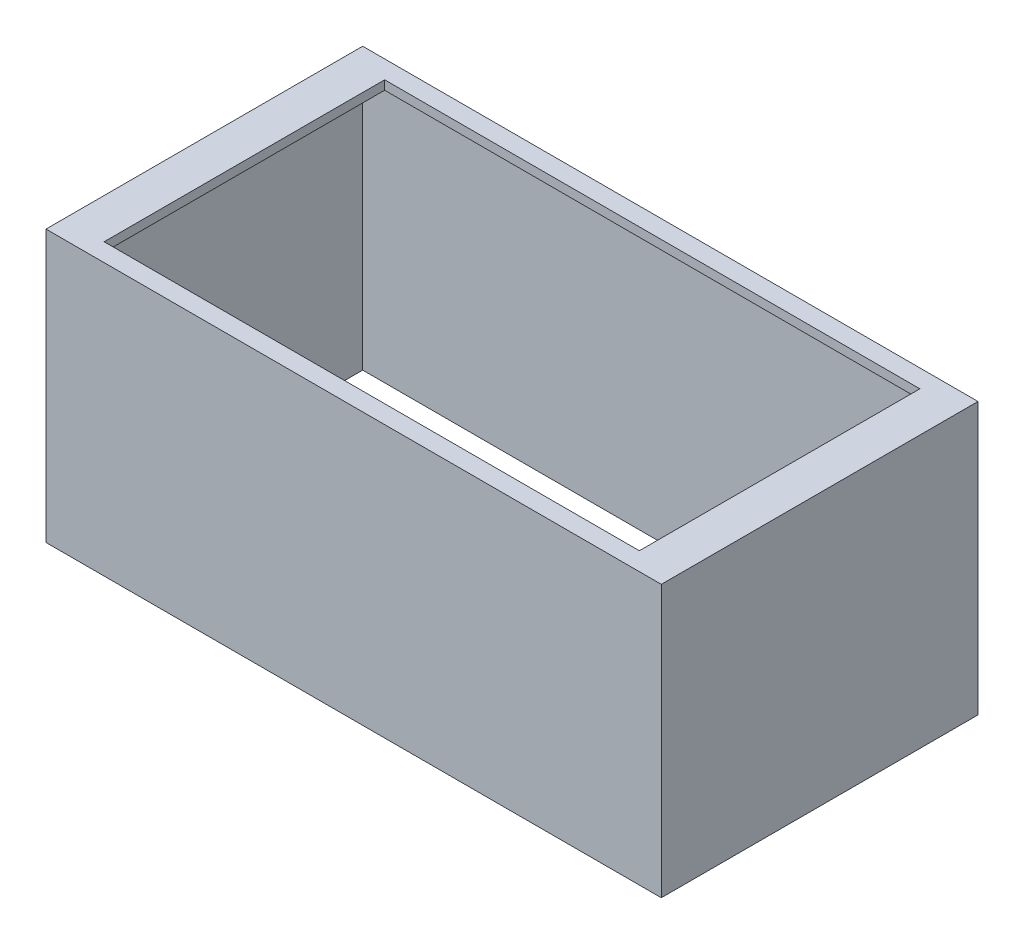
SolidWorks part; units mm, degrees
ref_plane "前视基准面" through (0, 0, 0) normal (0, 0, 1) x (1, 0, 0)
ref_plane "上视基准面" through (0, 0, 0) normal (0, 1, 0) x (1, 0, 0)
ref_plane "右视基准面" through (0, 0, 0) normal (1, 0, 0) x (0, 0, -1)
other "Configuration Table"
sketch "草图1" plane through (0, 0, 0) normal (0, 1, 0) x (1, 0, 0)
  line L1 (68, 35) -> (-68, 35)
  line L2 (68, 35) -> (68, -35)
  line L3 (68, -35) -> (-68, -35)
  line L4 (-68, 35) -> (-68, -35)
  line L5 (68, 35) -> (-68, -35) construction
  line L6 (68, -35) -> (-68, 35) construction
  point P0 (0, 0)
  dimension "D1" = 136
  dimension "D2" = 70
extrude "凸台-拉伸1" add sketch "草图1" along normal blind 60
sketch "草图2" plane through (0, 60, 0) normal (0, 1, 0) x (1, 0, 0)
  line L0 (-68, 0) -> (68, 0) construction
  line L1 (-59.15, 31) -> (59.15, 31)
  line L2 (-59.15, 31) -> (-59.15, -31)
  line L3 (-59.15, -31) -> (59.15, -31)
  line L4 (59.15, 31) -> (59.15, -31)
  line L5 (-68, 35) -> (-68, -35) construction
  line L6 (68, -35) -> (68, 35) construction
  line L7 (-59.15, 0) -> (59.15, 0) construction
  line L8 (0, 31) -> (0, -31) construction
  line L9 (0, 35) -> (0, -35) construction
  line L10 (68, 35) -> (-68, 35) construction
  line L11 (-68, -35) -> (68, -35) construction
  dimension "D1" = 62
  dimension "D2" = 118.3
extrude "切除-拉伸1" cut sketch "草图2" against normal blind 2
sketch "草图3" plane through (0, 0, 0) normal (0, -1, 0) x (1, 0, 0)
  line L1 (-66, 33) -> (66, 33)
  line L2 (-66, 33) -> (-66, -33)
  line L3 (-66, -33) -> (66, -33)
  line L4 (66, 33) -> (66, -33)
  dimension "D1" = 132
  dimension "D2" = 66
extrude "切除-拉伸2" cut sketch "草图3" against normal blind 58
